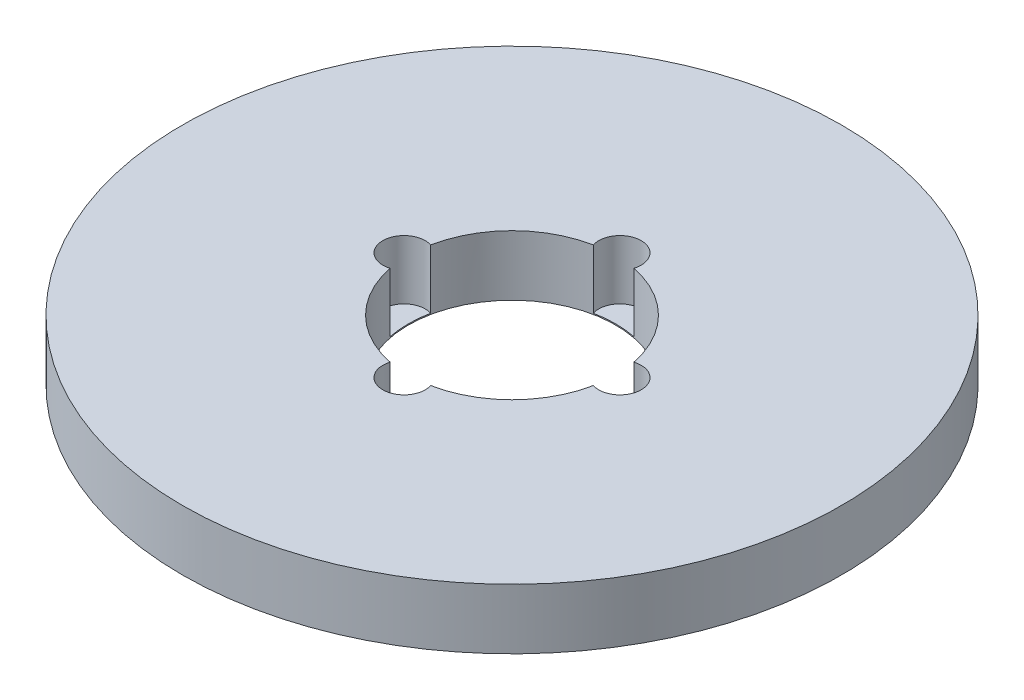
SolidWorks part; units mm, degrees
ref_plane "Front Plane" through (0, 0, 0) normal (0, 0, 1) x (1, 0, 0)
ref_plane "Top Plane" through (0, 0, 0) normal (0, 1, 0) x (1, 0, 0)
ref_plane "Right Plane" through (0, 0, 0) normal (1, 0, 0) x (0, 0, -1)
sketch "Sketch1" plane through (0, 0, 0) normal (0, 1, 0) x (1, 0, 0)
  circle A0 centre (0, 0) radius 87.5
  dimension "FLANGE_OD" = 175
extrude "Boss-Extrude1" add sketch "Sketch1" along normal blind 16
sketch "Sketch2" plane through (0, 0, 0) normal (0, 1, 0) x (1, 0, 0)
  circle A0 centre (0, 0) radius 27.5
  dimension "BORE_D" = 55
extrude "Cut-Extrude1" cut sketch "Sketch2" along normal through all
sketch "Sketch3" plane through (0, 16, 0) normal (0, 1, 0) x (1, 0, 0)
  circle A0 centre (0, 0) radius 28.6644 construction
  circle A1 centre (-28.6644, 0) radius 5.6414
  dimension "BOLT_D" = 11.2828
  dimension "BOLT_PCD" = 57.3288
extrude "Cut-Extrude2" cut sketch "Sketch3" against normal blind 15.7148
pattern_circular "CirPattern1" count 4 over 360 about axis through (0, 0, 0) along (0, 1, 0) of "Cut-Extrude2"
